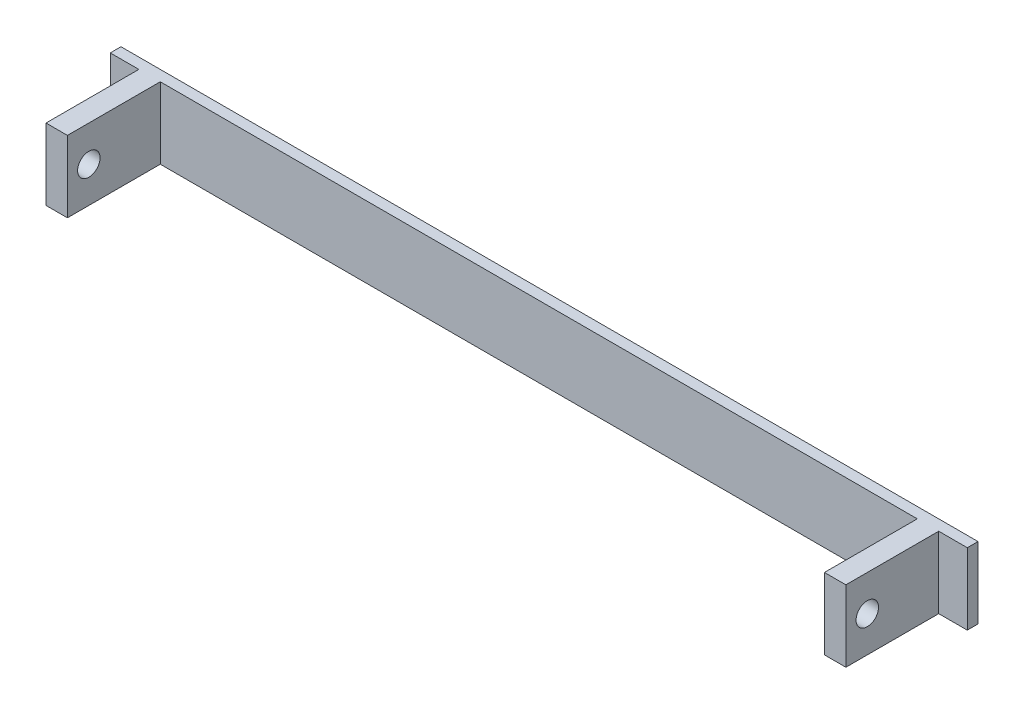
SolidWorks part; units mm, degrees
ref_plane "前视基准面" through (0, 0, 0) normal (0, 0, 1) x (1, 0, 0)
ref_plane "上视基准面" through (0, 0, 0) normal (0, 1, 0) x (1, 0, 0)
ref_plane "右视基准面" through (0, 0, 0) normal (1, 0, 0) x (0, 0, -1)
sketch "草图1" plane through (0, 0, 0) normal (0, 0, 1) x (1, 0, 0)
  line L1 (-60, -5) -> (60, -5)
  line L2 (-60, -5) -> (-60, 5)
  line L3 (-60, 5) -> (60, 5)
  line L4 (60, -5) -> (60, 5)
  line L5 (-60, -5) -> (60, 5) construction
  line L6 (-60, 5) -> (60, -5) construction
  point P0 (0, 0)
  dimension "D1" = 10
  dimension "D2" = 120
extrude "凸台-拉伸1" add sketch "草图1" along normal blind 1.5
sketch "草图2" plane through (0, 0, 1.5) normal (0, 0, 1) x (1, 0, 0)
  line L0 (60, 5) -> (-60, 5) construction
  line L1 (-56, 5) -> (-53, 5)
  line L2 (-56, 5) -> (-56, -5)
  line L3 (-56, -5) -> (-53, -5)
  line L4 (-53, 5) -> (-53, -5)
  line L5 (-60, -5) -> (60, -5) construction
  line L6 (60, -5) -> (60, 5) construction
  line L7 (53, 5) -> (56, 5)
  line L8 (53, 5) -> (53, -5)
  line L9 (53, -5) -> (56, -5)
  line L10 (56, 5) -> (56, -5)
  line L11 (-60, 5) -> (-60, -5) construction
  dimension "D1" = 3
  dimension "D2" = 4
  dimension "D3" = 3
  dimension "D4" = 4
extrude "凸台-拉伸2" add sketch "草图2" along normal blind 13
sketch "草图3" plane through (56, 0, 0) normal (1, 0, 0) x (0, 0, -1)
  line L2 (-14.5, 0) -> (-9.2904, 0) construction
  line L3 (-14.5, -5) -> (-14.5, 5) construction
  line L4 (0, -5) -> (0, 5) construction
  circle A0 centre (-11.5, 0) radius 1.575
  dimension "D1" = 3.15
  dimension "D2" = 11.5
extrude "切除-拉伸1" cut sketch "草图3" against normal up to surface (112 mm away) up to face at (-56, 0, 8)
